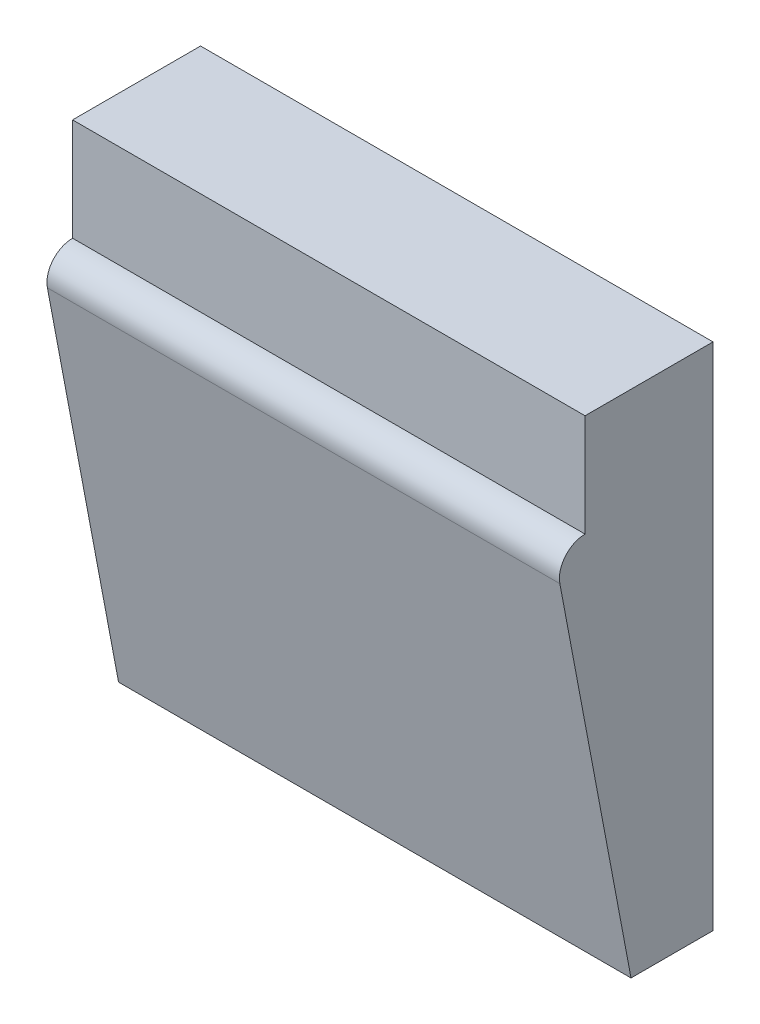
SolidWorks part; units mm, degrees
ref_plane "前视基准面" through (0, 0, 0) normal (0, 0, 1) x (1, 0, 0)
ref_plane "上视基准面" through (0, 0, 0) normal (0, 1, 0) x (1, 0, 0)
ref_plane "右视基准面" through (0, 0, 0) normal (1, 0, 0) x (0, 0, -1)
other "Configuration Table"
sketch "草图1" plane through (0, 0, 0) normal (1, 0, 0) x (0, 0, -1)
  line L0 (0, 0) -> (0.2, 0)
  line L1 (0.2, 0) -> (0.2, 31.8)
  line L2 (0.2, 31.8) -> (-6, 31.8)
  line L3 (-6, 31.8) -> (0, 0)
  dimension "D1" = 0.2
  dimension "D2" = 31.8
  dimension "D3" = 6.2
extrude "凸台-拉伸1" add sketch "草图1" along normal blind 20
sketch "草图3" plane through (0, 0, -0.2) normal (0, 0, -1) x (-1, 0, 0)
  line L0 (-10, 31.8) -> (-10, 25) construction
  line L1 (-20, 31.8) -> (0, 31.8) construction
  line L2 (-10, 0) -> (-10, 5) construction
  line L3 (-20, 0) -> (0, 0) construction
  circle A0 centre (-10, 25) radius 2.25
  circle A1 centre (-10, 5) radius 2.25
  dimension "D3" = 4.5
  dimension "D4" = 4.5
  dimension "D1" = 20
  dimension "D2" = 5
extrude "切除-拉伸1" cut sketch "草图3" against normal blind 2.5
fillet "圆角1" radius 1 2 edges at (10, 0, 0) (10, 31.8, 6)
sketch "草图4" plane through (20, 0, 0) normal (1, 0, 0) x (0, 0, -1)
  line L0 (0.2, 15.9) -> (-6.4564, 15.9) construction
  line L1 (0.2, 0) -> (0.2, 31.8) construction
  line L3 (-6.4564, 15.9) -> (3.7033, 15.9)
  line L4 (-6.4564, 15.9) -> (-6.4564, 0)
  line L5 (-6.4564, 0) -> (3.7033, 0)
  line L6 (3.7033, 15.9) -> (3.7033, 0)
extrude "切除-拉伸2" cut sketch "草图4" against normal blind 30
sketch "草图5" plane through (0, 0, 2.3) normal (0, 0, -1) x (-1, 0, 0)
  circle A0 centre (-10, 25) radius 1.5
  dimension "D1" = 3
extrude "切除-拉伸3" cut sketch "草图5" against normal blind 2
sketch "草图6" plane through (0, 31.8, 0) normal (0, 1, 0) x (1, 0, 0)
  line L4 (0, 0.2) -> (0, -4.7937)
  line L5 (0, -4.7937) -> (20, -4.7937)
  line L6 (20, -4.7937) -> (20, 0.2)
  line L7 (20, 0.2) -> (0, 0.2)
  line L8 (0, 0.2) -> (0, -4.7937)
  line L9 (0, -4.7937) -> (20, -4.7937)
  line L10 (20, -4.7937) -> (20, 0.2)
  line L11 (20, 0.2) -> (0, 0.2)
  dimension "D1" = 0
extrude "凸台-拉伸2" add sketch "草图6" along normal blind 4
sketch "草图7" plane through (0, 0, -0.2) normal (0, 0, -1) x (-1, 0, 0)
  line L0 (-10, 35.8) -> (-10, 30.8) construction
  line L1 (-20, 35.8) -> (0, 35.8) construction
  circle A0 centre (-10, 30.8) radius 2.1
  point P5 (-10, 31.5357)
  dimension "D1" = 4.2
  dimension "D2" = 5
extrude "切除-拉伸4" cut sketch "草图7" against normal blind 1.2
fillet "圆角2" radius 0.2 3 edges at (8.5, 25, 2.3) (7.75, 25, -0.2) (7.9, 30.8, -0.2)
